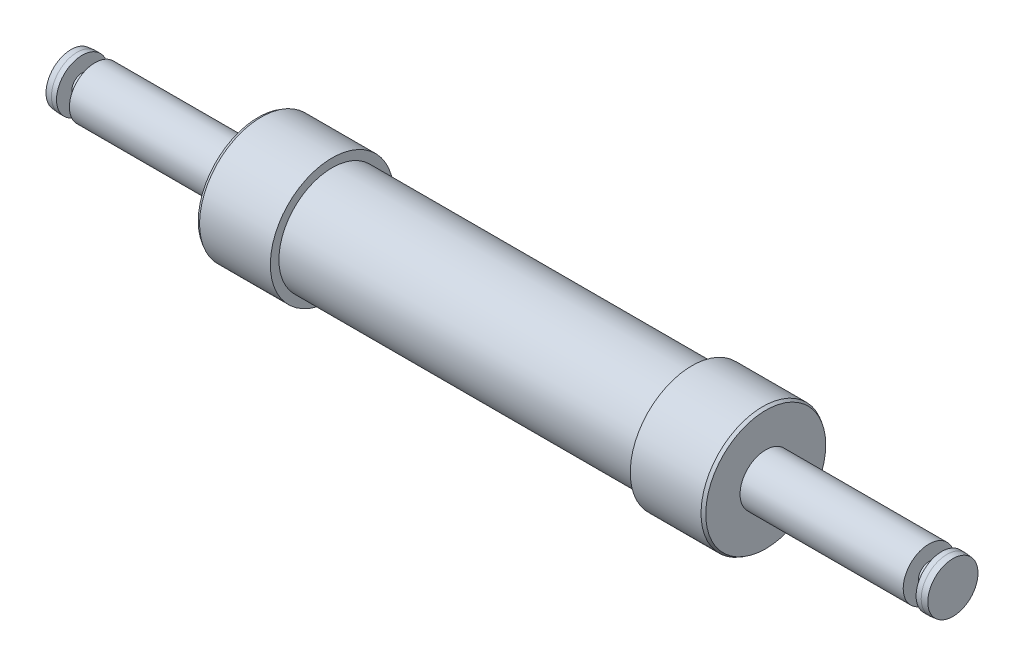
SolidWorks part; units mm, degrees
note: '?' marks a value the reader was unsure of.
material "Простая углеродистая сталь"
ref_plane "Спереди" through (0, 0, 0) normal (0, 0, 1) x (1, 0, 0)
ref_plane "Сверху" through (0, 0, 0) normal (0, 1, 0) x (1, 0, 0)
ref_plane "Справа" through (0, 0, 0) normal (1, 0, 0) x (0, 0, -1)
sketch "Эскиз1" plane through (0, 0, 0) normal (0, 0, 1) x (1, 0, 0)
  line L0 (0, 0) -> (0, 18)
  line L1 (0, 18) -> (20, 18)
  line L2 (20, 18) -> (20, 7.5)
  line L3 (20, 7.5) -> (73.5, 7.5)
  line L4 (73.5, 7.5) -> (73.5, 0)
  line L6 (0, 0) -> (73.5, 0)
  point P7 (73.5, 3.75)
  dimension "D1" = 20
  dimension "D2" = 53.5
  dimension "D3" = 73.5
  dimension "D4" = 18
  dimension "D5" = 7.5
revolve "Повернуть1" add sketch "Эскиз1" angle 360 about L6
mirror "Зеркальное отражение1" about plane through (0, 0, 0) normal (1, 0, 0) of bodies 103
chamfer "Фаска1" distance 1 angle 10 2 edges at (73.5, -7.5, 0) (-73.5, -7.5, 0) first distance on face at (20, -7.5, 0) first distance on face at (-20, -7.5, 0)
sketch "Эскиз3" plane through (-20, 0, 0) normal (-1, 0, 0) x (0, 0, 1)
  circle A0 centre (0, 0) radius 18 construction
  circle A1 centre (0, 0) radius 18
ref_axis "Ось1" through (20, 0, 0) along (-1, 0, 0)?
ref_axis "Ось2" through (-72.5, 0, 0) along (1, 0, 0)?
sketch "Эскиз5" plane through (0, 0, 0) normal (0, 0, 1) x (1, 0, 0)
  line L0 (-20, 7.5) -> (-72.5, 7.5) construction
  line L1 (-69.5, 3.05) -> (-71.65, 3.05)
  line L2 (-69.5, 3.05) -> (-69.5, 11.95)
  line L3 (-69.5, 11.95) -> (-71.65, 11.95)
  line L4 (-71.65, 3.05) -> (-71.65, 11.95)
  line L5 (-69.5, 3.05) -> (-71.65, 11.95) construction
  line L6 (-69.5, 11.95) -> (-71.65, 3.05) construction
  line L7 (-73.5, 7.3237) -> (-73.5, -7.3237) construction
  line L8 (0, 0) -> (-73.5, 0) construction
  point P0 (-70.575, 7.5)
  dimension "D1" = 2.15
  dimension "D2" = 1.85
  dimension "D3" = 11.95
revolve "Вырез-Повернуть3" cut sketch "Эскиз5" angle 360 about L8
mirror "Зеркальное отражение5" about plane through (0, 0, 0) normal (1, 0, 0) of "Вырез-Повернуть3"
extrude "Бобышка-Вытянуть1" add sketch "Эскиз3" along normal blind 22.3
sketch "Эскиз6" plane through (20, 0, 0) normal (1, 0, 0) x (0, 0, -1)
  circle A1 centre (0, 0) radius 18
  circle A2 centre (0, 0) radius 18
  dimension "D1" = 0
extrude "Бобышка-Вытянуть2" add sketch "Эскиз6" along normal blind 22.3
chamfer "Фаска2" distance 0.5 angle 45 2 edges at (42.3, 0, -18) (-42.3, 0, 18)
scale "Scale1" scale about origin uniform scaling no x scale factor 0.7 y scale factor 0.4 z scale factor 0.4
sketch "Sketch1" plane through (0, 0, 0) normal (0, 0, 1) x (1, 0, 0)
  line L0 (29.26, 7.2) -> (-29.26, 7.2) construction
  line L1 (21, 6.2) -> (-21, 6.2)
  line L2 (21, 6.2) -> (21, 8.2)
  line L3 (21, 8.2) -> (-21, 8.2)
  line L4 (-21, 6.2) -> (-21, 8.2)
  line L5 (21, 6.2) -> (-21, 8.2) construction
  line L6 (21, 8.2) -> (-21, 6.2) construction
  line L7 (-28.6049, 0) -> (26.076, 0) construction
  point P0 (0, 7.2)
  dimension "D1" = 42
  dimension "D2" = 2
revolve "Cut-Revolve3" cut sketch "Sketch1" angle 360 about L7
